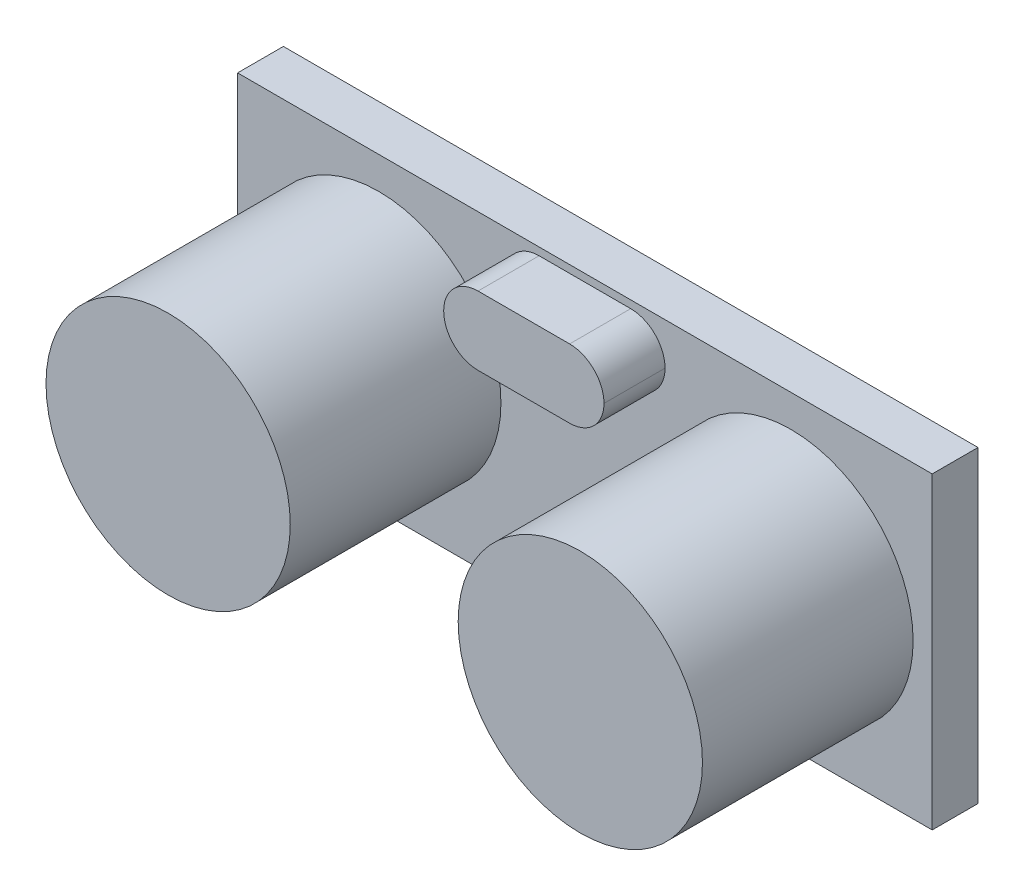
SolidWorks part; units mm, degrees
ref_plane "Спереди" through (0, 0, 0) normal (0, 0, 1) x (1, 0, 0)
ref_plane "Сверху" through (0, 0, 0) normal (0, 1, 0) x (1, 0, 0)
ref_plane "Справа" through (0, 0, 0) normal (1, 0, 0) x (0, 0, -1)
sketch "Sketch1" plane through (0, 0, 0) normal (0, 0, 1) x (1, 0, 0)
  line L1 (-22.75, 10.1) -> (22.75, 10.1)
  line L2 (-22.75, 10.1) -> (-22.75, -10.1)
  line L3 (-22.75, -10.1) -> (22.75, -10.1)
  line L4 (22.75, 10.1) -> (22.75, -10.1)
  line L5 (-22.75, 10.1) -> (22.75, -10.1) construction
  line L6 (-22.75, -10.1) -> (22.75, 10.1) construction
  point P0 (0, 0)
  dimension "D1" = 45.5
  dimension "D2" = 20.2
extrude "Boss-Extrude1" add sketch "Sketch1" along normal blind 3
sketch "Sketch2" plane through (0, 0, 3) normal (0, 0, 1) x (1, 0, 0)
  line L0 (0, 0) -> (13.5, 0) construction
  line L1 (0, 0) -> (-13.5, 0) construction
  circle A0 centre (-13.5, 0) radius 8
  circle A1 centre (13.5, 0) radius 8
  dimension "D1" = 16
  dimension "D2" = 27
extrude "Boss-Extrude2" add sketch "Sketch2" along normal blind 13.8
sketch "Sketch3" plane through (0, 0, 3) normal (0, 0, 1) x (1, 0, 0)
  line L0 (0, 7.35) -> (0, 0) construction
  line L1 (-5.25, 9.6) -> (5.25, 9.6)
  line L2 (-5.25, 9.6) -> (-5.25, 5.1)
  line L3 (-5.25, 5.1) -> (5.25, 5.1)
  line L4 (5.25, 9.6) -> (5.25, 5.1)
  line L5 (-5.25, 9.6) -> (5.25, 5.1) construction
  line L6 (-5.25, 5.1) -> (5.25, 9.6) construction
  line L7 (22.75, 10.1) -> (-22.75, 10.1) construction
  point P0 (0, 7.35)
  dimension "D1" = 4.5
  dimension "D2" = 10.5
  dimension "D3" = 0.5
extrude "Boss-Extrude3" add sketch "Sketch3" along normal blind 4
fillet "Fillet1" radius 2.25 4 edges at (-5.25, 5.1, 5) (-5.25, 9.6, 5) (5.25, 5.1, 5) (5.25, 9.6, 5)
sketch "Sketch4" plane through (0, 0, 0) normal (0, 0, -1) x (-1, 0, 0)
  line L0 (0, 0) -> (0, -8.83) construction
  line L1 (22.75, -10.1) -> (-22.75, -10.1) construction
  line L2 (-5.08, -7.56) -> (5.08, -7.56)
  line L3 (-5.08, -7.56) -> (-5.08, -10.1)
  line L4 (-5.08, -10.1) -> (5.08, -10.1)
  line L5 (5.08, -7.56) -> (5.08, -10.1)
  line L6 (-5.08, -7.56) -> (5.08, -10.1) construction
  line L7 (-5.08, -10.1) -> (5.08, -7.56) construction
  dimension "D1" = 2.54
  dimension "D2" = 10.16
extrude "Boss-Extrude4" add sketch "Sketch4" along normal blind 10 and the other way blind 5
